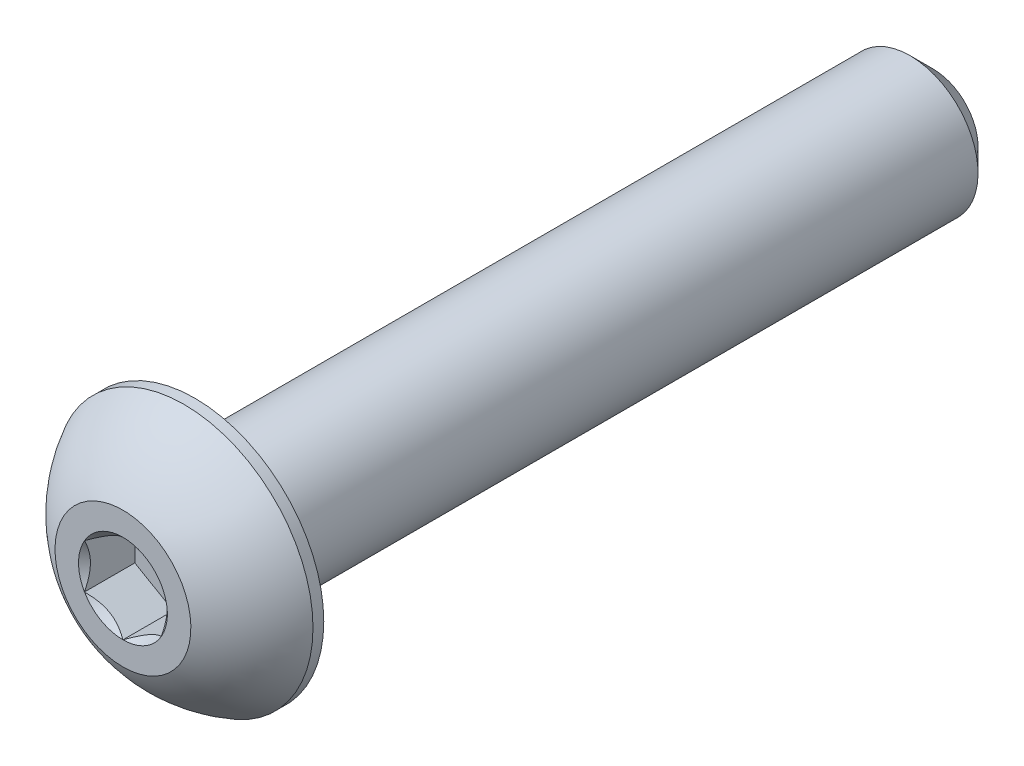
SolidWorks part; units mm, degrees
ref_plane "Front" through (0, 0, 0) normal (0, 0, 1) x (1, 0, 0)
ref_plane "Top" through (0, 0, 0) normal (0, 1, 0) x (1, 0, 0)
ref_plane "Right" through (0, 0, 0) normal (1, 0, 0) x (0, 0, -1)
sketch "Sketch1" plane through (0, 0, 0) normal (1, 0, 0) x (0, 0, -1)
  line L2 (1.8542, 1.7526) -> (20.9042, 1.7526)
  line L3 (20.9042, 1.7526) -> (20.9042, 0)
  line L4 (20.9042, 0) -> (1.8542, 0)
  line L6 (1.5761, 3.3274) -> (1.8542, 3.3274) construction
  line L7 (20.9042, 1.7526) -> (20.9042, -1.7526) construction
  line L8 (0, 0) -> (1.8542, 0) construction
  line L9 (1.8542, 3.3274) -> (1.8542, -3.3274) construction
  line L11 (1.8542, 1.7526) -> (1.8542, 0)
  line L13 (0, 0.9922) -> (0, -0.9922) construction
  line L14 (0, 0.9922) -> (0, 1.7526) construction
  arc A3 (0, 1.7526) -> (1.5761, 3.3274) centre (3.326, 0) cw construction
  dimension "D1" = 0.2781
revolve "Revolve1" add sketch "Sketch1" angle 360 mid plane about L4
sketch "Sketch3" plane through (0, 0, -20.9042) normal (0, 0, -1) x (-1, 0, 0)
  circle A0 centre (0, 0) radius 1.7526
curve "Helix/Spiral1" [suppressed] pitch 0.7937 height 20.9042 turns 26.336
sketch "Sketch2" plane through (0, 0, 0) normal (1, 0, 0) x (0, 0, -1)
  line L0 (20.9042, 1.7526) -> (21.5987, 1.7526)
  line L1 (21.5987, 1.7526) -> (21.3011, 1.237)
  line L2 (21.3011, 1.237) -> (21.2019, 1.237)
  line L3 (21.2019, 1.237) -> (20.9042, 1.7526)
  line L4 (21.053, 1.4948) -> (21.4499, 1.4948) construction
  dimension "D1" = 60
  dimension "D2" = 0.0992
  dimension "D3" = 0.3969
chamfer "Chamfer1" distance 0.5953 angle 45 1 edges at (0, 1.7526, -20.9042)
sweep "Cut-Sweep1" [suppressed] cut profiles "Sketch2" path "Helix/Spiral1"
sketch "Sketch7" plane through (0, 0, 0) normal (1, 0, 0) x (0, 0, -1)
  line L6 (1.5761, 3.3274) -> (1.8542, 3.3274) construction
  line L8 (0, 0) -> (1.8542, 0) construction
  line L11 (1.8542, 3.3274) -> (1.8542, -3.3274) construction
  line L12 (1.5761, 3.3274) -> (1.8542, 3.3274)
  line L13 (0, 0) -> (1.8542, 0)
  line L14 (0, 0.9922) -> (0, -0.9922) construction
  line L15 (1.8542, 3.3274) -> (1.8542, 0)
  line L16 (0, 1.7526) -> (0, 0)
  arc A2 (1.5761, 3.3274) -> (0, 1.7526) centre (3.326, 0) ccw construction
  arc A3 (1.5761, 3.3274) -> (0, 1.7526) centre (3.326, 0) ccw
revolve "Revolve2" add sketch "Sketch7" angle 360 mid plane about L13
sketch "Sketch5" plane through (0, 0, 0) normal (0, 0, 1) x (1, 0, 0)
  line L1 (0.9922, -0.5728) -> (0.9922, 0.5728)
  line L2 (0.9922, 0.5728) -> (0, 1.1457)
  line L3 (0, 1.1457) -> (-0.9922, 0.5728)
  line L4 (-0.9922, 0.5728) -> (-0.9922, -0.5728)
  line L5 (-0.9922, -0.5728) -> (0, -1.1457)
  line L6 (0, -1.1457) -> (0.9922, -0.5728)
  circle A0 centre (0, 0) radius 0.9922 construction
extrude "Cut-Extrude2" cut sketch "Sketch5" against normal blind 1.2979
sketch "Sketch6" plane through (0, 0, 0) normal (0, 0, 1) x (1, 0, 0)
  circle A0 centre (0, 0) radius 1.1457
extrude "Cut-Extrude3" cut sketch "Sketch6" against normal blind 1.2979 draft 45
sketch "Sketch9" [suppressed] plane through (0, 0, -1.8542) normal (0, 0, 1) x (1, 0, 0)
  circle A2 centre (0, 0) radius 1.7526
extrude "Boss-Extrude2" [suppressed] add sketch "Sketch9" against normal offset from surface (19.05 mm away) 22.225
sketch "Sketch10" plane through (0, 0, 0) normal (1, 0, 0) x (0, 0, -1)
  line L0 (20.9042, 1.7526) -> (20.9042, -1.7526) construction
  point P0 (19.7136, -1.7526)
  dimension "D1" = 1.1906
equation "\"D3@Helix/Spiral1\" = \"Lg@Sketch1\" + \"Head Ht@Sketch1\""
equation "\"D2@Sketch2\" = \"D4@Helix/Spiral1\" * .125"
equation "\"D3@Sketch2\" = \"D4@Helix/Spiral1\" * .5"
equation "\"D1@Chamfer1\" = \"D4@Helix/Spiral1\" * .75"
equation "\"D1@Cut-Extrude2\" = \"Head Ht@Sketch1\" * .7"
equation "\"D1@Sketch1\" = \"Head Ht@Sketch1\" * .15"
equation "\"D1@Sketch10\" = \"D4@Helix/Spiral1\" * 1.5"
equation "\"D1@Cut-Extrude3\" = \"D1@Cut-Extrude2\""
